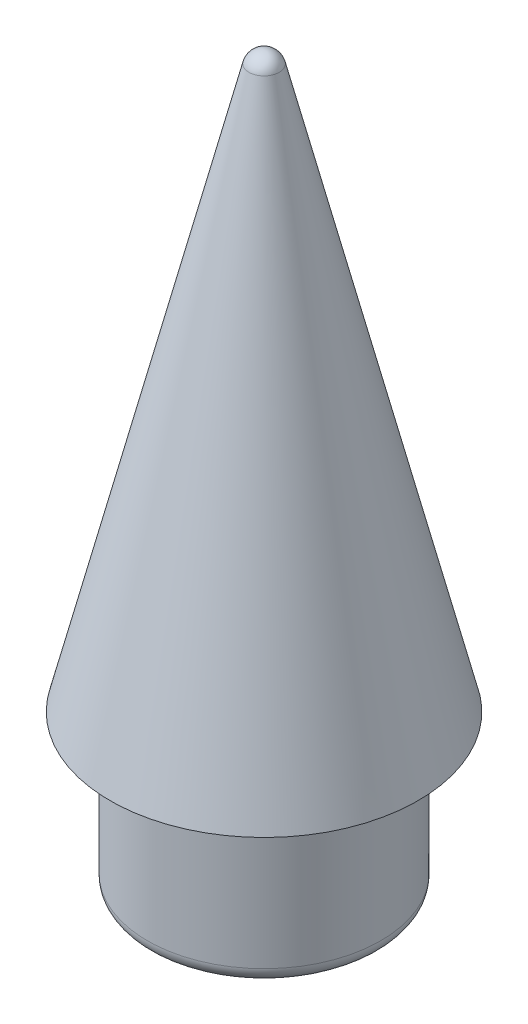
SolidWorks part; units mm, degrees
material "6061 Alloy"
ref_plane "Front Plane" through (0, 0, 0) normal (0, 0, 1) x (1, 0, 0)
ref_plane "Top Plane" through (0, 0, 0) normal (0, 1, 0) x (1, 0, 0)
ref_plane "Right Plane" through (0, 0, 0) normal (1, 0, 0) x (0, 0, -1)
sketch "Sketch2" plane through (0, 0, 0) normal (0, 0, 1) x (1, 0, 0)
  line L0 (0, 0) -> (8.255, 0)
  line L1 (9.525, 1.27) -> (9.525, 11.43)
  line L2 (10.795, 12.7) -> (10.9504, 12.7)
  line L3 (0, 0) -> (0, 63.5) construction
  line L4 (12.1832, 14.2751) -> (1.2328, 58.519)
  line L5 (0, 59.4839) -> (0.2637, 59.4839) construction
  line L6 (0, 59.4839) -> (0, 0)
  arc A0 (8.255, 0) -> (9.525, 1.27) centre (8.255, 1.27) ccw
  arc A1 (9.525, 11.43) -> (10.795, 12.7) centre (10.795, 11.43) cw
  arc A2 (10.9504, 12.7) -> (12.1832, 14.2751) centre (10.9504, 13.97) ccw
  arc A3 (1.2328, 58.519) -> (0, 59.4839) centre (0, 58.2139) ccw
  point P8 (9.525, 0)
  point P13 (12.573, 12.7)
  dimension "D5" = 1.27
  dimension "D6" = 1.27
  dimension "D1" = 12.573
  dimension "D2" = 9.525
  dimension "D3" = 50.8
  dimension "D4" = 12.7
  dimension "D7" = 4.0161
revolve "Revolve1" add sketch "Sketch2" angle 360 about L3
other "DeleteFace1" face at (0, 14.2751, -12.1832) and patch yes
